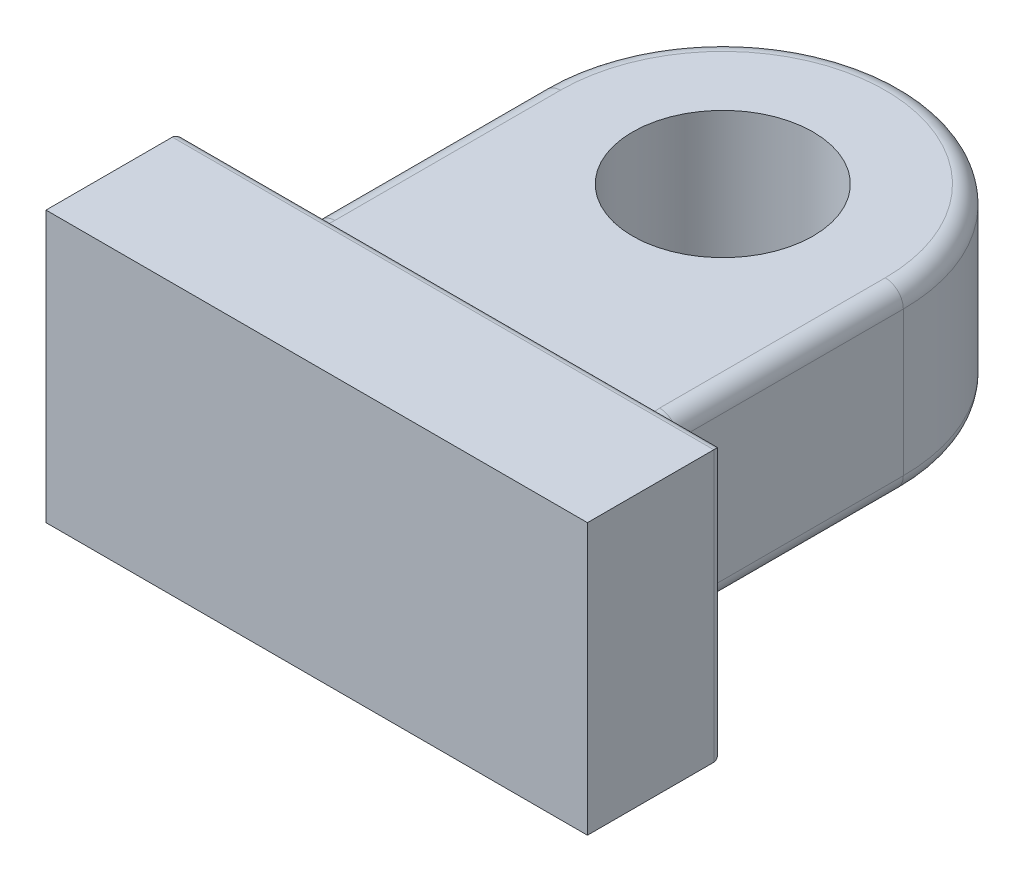
SolidWorks part; units mm, degrees
ref_plane "Front Plane" through (0, 0, 0) normal (0, 0, 1) x (1, 0, 0)
ref_plane "Top Plane" through (0, 0, 0) normal (0, 1, 0) x (1, 0, 0)
ref_plane "Right Plane" through (0, 0, 0) normal (1, 0, 0) x (0, 0, -1)
sketch "Sketch1" plane through (0, 0, 0) normal (0, 0, 1) x (1, 0, 0)
  line L1 (0, 0) -> (1524, 0)
  line L2 (0, 0) -> (0, -762)
  line L3 (0, -762) -> (1524, -762)
  line L4 (1524, 0) -> (1524, -762)
  dimension "D1" = 1524
  dimension "D2" = 762
extrude "Boss-Extrude1" add sketch "Sketch1" along normal blind 381
ref_plane "Plane1" through (0, -381, 0) normal (0, -1, 0) x (-1, 0, 0)
sketch "Sketch3" plane through (0, -381, 0) normal (0, -1, 0) x (-1, 0, 0)
  line L0 (-1270, 762) -> (-1270, 0)
  line L1 (0, 0) -> (-1524, 0) construction
  line L2 (-254, 762) -> (-254, 0)
  line L3 (-254, 0) -> (-1270, 0)
  arc A0 (-254, 762) -> (-1270, 762) centre (-762, 762) ccw
  circle A1 centre (-762, 762) radius 254
  dimension "D1" = 1016
  dimension "D2" = 508
  dimension "D3" = 762
  dimension "D4" = 254
extrude "Boss-Extrude2" add sketch "Sketch3" along normal mid plane 508
fillet "Fillet1" radius 127 2 edges at (1270, -381, 0) (254, -381, 0)
fillet "Fillet2" radius 50.8 10 edges at (216.8026, -127, -37.1974) (1307.1974, -127, -37.1974) (216.8026, -635, -37.1974) (1307.1974, -635, -37.1974) (1270, -127, -444.5) (762, -127, -1270) (254, -127, -444.5) (254, -635, -444.5) (1270, -635, -444.5) (762, -635, -1270)
fillet "Fillet3" radius 25.4 10 edges at (762, -762, 0) (1524, -381, 0) (762, 0, 0) (0, -381, 0) (211.3972, -628.2435, 0) (211.3972, -133.7565, 0) (762, -127, 0) (1312.6028, -133.7565, 0) (1312.6028, -628.2435, 0) (762, -635, 0)
sketch "Sketch4" plane through (0, 0, 381) normal (0, 0, 1) x (1, 0, 0)
  line L0 (762, 0) -> (762, -762) construction
  line L1 (1524, 0) -> (0, 0) construction
  line L2 (0, -762) -> (1524, -762) construction
